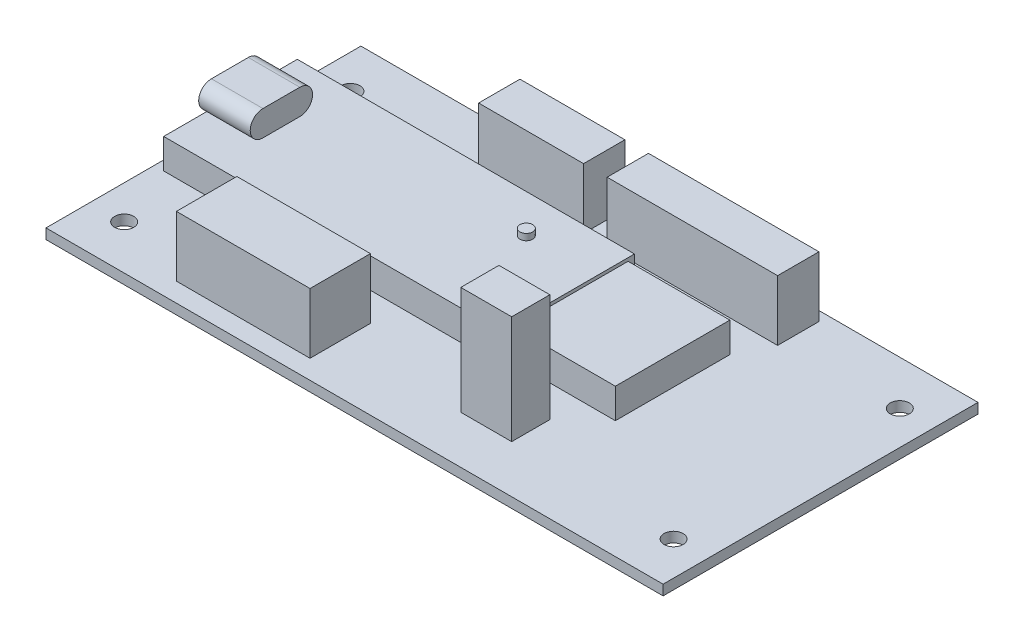
SolidWorks part; units mm, degrees
ref_plane "Front Plane" through (0, 0, 0) normal (0, 0, 1) x (1, 0, 0)
ref_plane "Top Plane" through (0, 0, 0) normal (0, 1, 0) x (1, 0, 0)
ref_plane "Right Plane" through (0, 0, 0) normal (1, 0, 0) x (0, 0, -1)
sketch "Sketch1" plane through (0, 0, 0) normal (0, 1, 0) x (1, 0, 0)
  line L1 (-48.5, -24.75) -> (48.5, -24.75)
  line L2 (-48.5, -24.75) -> (-48.5, 24.75)
  line L3 (-48.5, 24.75) -> (48.5, 24.75)
  line L4 (48.5, -24.75) -> (48.5, 24.75)
  line L5 (-48.5, -24.75) -> (48.5, 24.75) construction
  line L6 (-48.5, 24.75) -> (48.5, -24.75) construction
  line L7 (43.18, -17.78) -> (-43.18, -17.78) construction
  line L8 (43.18, -17.78) -> (43.18, 17.78) construction
  line L9 (43.18, 17.78) -> (-43.18, 17.78) construction
  line L10 (-43.18, -17.78) -> (-43.18, 17.78) construction
  line L11 (43.18, -17.78) -> (-43.18, 17.78) construction
  line L12 (43.18, 17.78) -> (-43.18, -17.78) construction
  circle A0 centre (-43.18, 17.78) radius 1.5
  circle A1 centre (-43.18, -17.78) radius 1.5
  circle A2 centre (43.18, 17.78) radius 1.5
  circle A3 centre (43.18, -17.78) radius 1.5
  point P0 (0, 0)
  point P5 (0, 0)
  dimension "D5" = 3
  dimension "D1" = 97
  dimension "D2" = 49.5
  dimension "D3" = 35.56
  dimension "D4" = 86.36
extrude "Boss-Extrude1" add sketch "Sketch1" along normal blind 1.6
sketch "Sketch2" plane through (0, 1.6, 0) normal (0, 1, 0) x (1, 0, 0)
  line L0 (-48.5, 24.75) -> (-48.5, -24.75) construction
  line L1 (-22, 23.25) -> (-5.5, 23.25)
  line L2 (-22, 23.25) -> (-22, 16.75)
  line L3 (-22, 16.75) -> (-5.5, 16.75)
  line L4 (-5.5, 23.25) -> (-5.5, 16.75)
  line L5 (-1.8, 23.25) -> (25, 23.25)
  line L6 (-1.8, 23.25) -> (-1.8, 16.75)
  line L7 (-1.8, 16.75) -> (25, 16.75)
  line L8 (25, 23.25) -> (25, 16.75)
  line L9 (-31, -12.25) -> (-10, -12.25)
  line L10 (-31, -12.25) -> (-31, -21.75)
  line L11 (-31, -21.75) -> (-10, -21.75)
  line L12 (-10, -12.25) -> (-10, -21.75)
  line L13 (-47, 13.25) -> (6, 13.25)
  line L14 (-47, 13.25) -> (-47, -7.75)
  line L15 (-47, -7.75) -> (6, -7.75)
  line L16 (6, 13.25) -> (6, -7.75)
  line L17 (9.2, -11.25) -> (17.2, -11.25)
  line L18 (9.2, -11.25) -> (9.2, -17.25)
  line L19 (9.2, -17.25) -> (17.2, -17.25)
  line L20 (17.2, -11.25) -> (17.2, -17.25)
  line L21 (6.5, 11.75) -> (22.5, 11.75)
  line L22 (6.5, 11.75) -> (6.5, -6.25)
  line L23 (6.5, -6.25) -> (22.5, -6.25)
  line L24 (22.5, 11.75) -> (22.5, -6.25)
  line L25 (48.5, -24.75) -> (48.5, 24.75) construction
  line L26 (48.5, 24.75) -> (-48.5, 24.75) construction
  line L27 (-48.5, -24.75) -> (48.5, -24.75) construction
  line L28 (6, 2.75) -> (22.5, 2.75) construction
  dimension "D1" = 1.5
  dimension "D2" = 26.5
  dimension "D3" = 16.5
  dimension "D4" = 3.7
  dimension "D5" = 26.8
  dimension "D6" = 23.5
  dimension "D7" = 1.5
  dimension "D8" = 6.5
  dimension "D9" = 53
  dimension "D10" = 21
  dimension "D11" = 11.5
  dimension "D12" = 9.5
  dimension "D13" = 21
  dimension "D14" = 3
  dimension "D15" = 17.5
  dimension "D16" = 0.5
  dimension "D17" = 18
  dimension "D18" = 16
  dimension "D19" = 8
  dimension "D20" = 6
  dimension "D21" = 7.5
  dimension "D22" = 19.2
extrude "Boss-Extrude2" add sketch "Sketch2" along normal blind 9.5 contours L8 L5 L6 L7 | L4 L1 L2 L3 | L12 L9 L10 L11 region at (-13.75, 1.6, -20) region at (11.6, 1.6, -20) region at (-20.5, 1.6, 17)
extrude "Boss-Extrude3" add sketch "Sketch2<3>" along normal blind 4.7 contours L16 L13 L14 L15 | L28 L22 L23 L24 | L22 L28 L24 L21 region at (14.5, 1.6, -7.25) region at (14.5, 1.6, 1.75) region at (-20.5, 1.6, -2.75)
sketch "Sketch2<3>" plane through (0, 1.6, 0) normal (0, 1, 0) x (1, 0, 0) same geometry as "Sketch2"
extrude "Boss-Extrude4" add sketch "Sketch2<4>" along normal blind 17 contours L20 L17 L18 L19 region at (13.2, 1.6, 14.25)
sketch "Sketch2<4>" plane through (0, 1.6, 0) normal (0, 1, 0) x (1, 0, 0) same geometry as "Sketch2"
sketch "Sketch3" plane through (0, 6.3, 0) normal (0, 1, 0) x (1, 0, 0)
  line L0 (-47, 13.25) -> (-47, -7.75) construction
  line L1 (-47, 13.25) -> (6, 13.25) construction
  circle A0 centre (-5, 7.25) radius 1
  dimension "D1" = 42
  dimension "D3" = 2
  dimension "D2" = 6
extrude "Boss-Extrude5" add sketch "Sketch3" along normal blind 1
sketch "Sketch4" plane through (-47, 0, 0) normal (-1, 0, 0) x (0, 0, 1)
  line L0 (-5.65, 8.3) -> (0.15, 8.3) construction
  line L1 (-5.65, 10.3) -> (0.15, 10.3)
  line L2 (-5.65, 6.3) -> (0.15, 6.3)
  line L3 (-2.75, 8.3) -> (-2.75, 6.3) construction
  line L4 (-13.25, 6.3) -> (7.75, 6.3) construction
  arc A0 (-5.65, 10.3) -> (-5.65, 6.3) centre (-5.65, 8.3) ccw
  arc A1 (0.15, 6.3) -> (0.15, 10.3) centre (0.15, 8.3) ccw
  point P2 (-2.75, 8.3)
  dimension "D1" = 9.8
  dimension "D2" = 4
extrude "Boss-Extrude6" add sketch "Sketch4" against normal blind 8 and the other way blind 0.1
